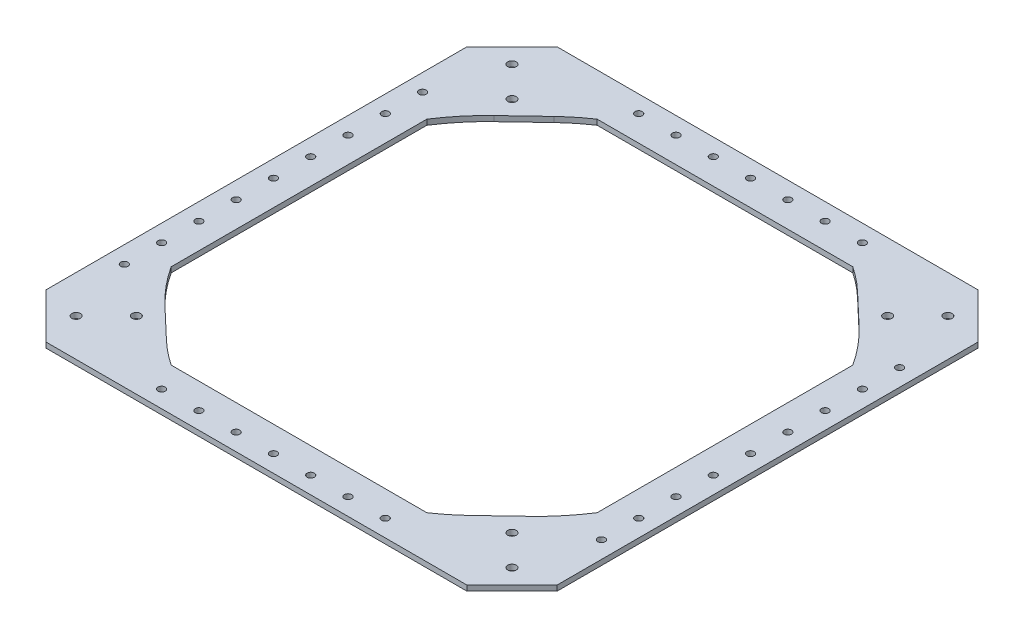
SolidWorks part; units mm, degrees
ref_plane "Front Plane" through (0, 0, 0) normal (0, 0, 1) x (1, 0, 0)
ref_plane "Top Plane" through (0, 0, 0) normal (0, 1, 0) x (1, 0, 0)
ref_plane "Right Plane" through (0, 0, 0) normal (1, 0, 0) x (0, 0, -1)
sketch "Sketch1" plane through (0, 0, 0) normal (0, 1, 0) x (1, 0, 0)
  line L0 (-152.4, 68.2596) -> (-125.4592, 95.2004)
  line L1 (-125.4592, 95.2004) -> (125.4592, 95.2004)
  line L2 (-152.4, 68.2596) -> (-152.4, -182.6588)
  line L3 (152.4, 68.2596) -> (152.4, -182.6588)
  line L4 (152.4, 68.2596) -> (125.4592, 95.2004)
  line L5 (0, 95.2004) -> (0, -209.5996) construction
  line L6 (-152.4, -57.1996) -> (152.4, -57.1996) construction
  line L7 (152.4, -182.6588) -> (125.4592, -209.5996)
  line L8 (-125.4592, -209.5996) -> (125.4592, -209.5996)
  line L9 (-152.4, -182.6588) -> (-125.4592, -209.5996)
  point P9 (0, -57.1996)
  point P11 (0, -57.1996)
  dimension "D1" = 304.8
  dimension "D2" = 304.8
  dimension "D3" = 38.1
  dimension "D4" = 45
extrude "Boss-Extrude1" add sketch "Sketch1" along normal blind 3.175
sketch "Sketch2" plane through (0, 3.175, 0) normal (0, 1, 0) x (1, 0, 0)
  line L0 (-76.2, 69.8004) -> (76.2, 69.8004)
  line L2 (127, -133.3996) -> (127, 19.0004)
  line L3 (90.4661, 58.3749) -> (108.8729, 40.884)
  line L4 (-127, -133.3996) -> (-127, 19.0004)
  line L5 (125.4592, 95.2004) -> (-125.4592, 95.2004) construction
  line L9 (-152.4, 68.2596) -> (-152.4, -182.6588) construction
  line L10 (-125.4592, 95.2004) -> (-152.4, 68.2596) construction
  line L12 (90.4661, -172.7741) -> (108.8729, -155.2832)
  line L13 (-76.2, -184.1996) -> (76.2, -184.1996)
  line L14 (-90.4661, -172.7741) -> (-108.8729, -155.2832)
  line L20 (-125.4592, 95.2004) -> (-90.4661, 58.3749) construction
  line L21 (-125.4592, 95.2004) -> (-143.4197, 77.2399) construction
  line L22 (-143.4197, 77.2399) -> (-108.8729, 40.884) construction
  line L23 (-90.4661, 58.3749) -> (-108.8729, 40.884)
  line L24 (0, 95.2004) -> (0, -259.712) construction
  line L25 (-152.4, -57.1996) -> (213.1094, -57.1996) construction
  arc A0 (-90.4661, 58.3749) -> (-76.2, 69.8004) centre (-15.9731, -20.019) cw
  arc A1 (-108.8729, 40.884) -> (-127, 19.0004) centre (-26.517, -45.7845) ccw
  arc A2 (108.8729, 40.884) -> (127, 19.0004) centre (26.517, -45.7845) cw
  arc A3 (90.4661, 58.3749) -> (76.2, 69.8004) centre (15.9731, -20.019) ccw
  arc A4 (108.8729, -155.2832) -> (127, -133.3996) centre (26.517, -68.6147) ccw
  arc A5 (90.4661, -172.7741) -> (76.2, -184.1996) centre (15.9731, -94.3802) cw
  arc A6 (-90.4661, -172.7741) -> (-76.2, -184.1996) centre (-15.9731, -94.3802) ccw
  arc A7 (-108.8729, -155.2832) -> (-127, -133.3996) centre (-26.517, -68.6147) cw
  point P19 (0, 69.8004)
  point P21 (127, -57.1996)
  point P46 (-127, -57.1996)
  dimension "D1" = 25.4
  dimension "D4" = 25.4
  dimension "D5" = 25.4
  dimension "D9" = 50.8
  dimension "D10" = 76.2
  dimension "D11" = 76.2
extrude "Cut-Extrude1" cut sketch "Sketch2" against normal through all
sketch "Sketch4" plane through (0, 3.175, 0) normal (0, 1, 0) x (1, 0, 0)
  line L0 (-152.4, -57.1996) -> (171.6111, -57.1996) construction
  line L1 (-152.4, 68.2596) -> (-152.4, -182.6588) construction
  line L2 (125.4592, 95.2004) -> (-125.4592, 95.2004) construction
  line L3 (0, -57.1996) -> (0, -217.7016) construction
  line L4 (152.4, -182.6588) -> (152.4, 68.2596) construction
  line L5 (0, -57.1996) -> (0, 293.0757) construction
  circle A0 centre (0, 85.0404) radius 2.159
  circle A1 centre (-44.45, 85.0404) radius 2.159
  circle A2 centre (44.45, 85.0404) radius 2.159
  circle A3 centre (-22.225, 85.0404) radius 2.159
  circle A4 centre (22.225, 85.0404) radius 2.159
  circle A5 centre (-142.24, -57.1996) radius 2.159
  circle A6 centre (-142.24, -34.9746) radius 2.159
  circle A7 centre (-142.24, -12.7496) radius 2.159
  circle A8 centre (142.24, -57.1996) radius 2.159
  circle A9 centre (142.24, -34.9746) radius 2.159
  circle A10 centre (142.24, -12.7496) radius 2.159
  circle A11 centre (142.24, -101.6496) radius 2.159
  circle A12 centre (142.24, -79.4246) radius 2.159
  circle A13 centre (-142.24, -101.6496) radius 2.159
  circle A14 centre (-142.24, -79.4246) radius 2.159
  circle A15 centre (22.225, -199.4396) radius 2.159
  circle A16 centre (-22.225, -199.4396) radius 2.159
  circle A17 centre (44.45, -199.4396) radius 2.159
  circle A18 centre (-44.45, -199.4396) radius 2.159
  circle A19 centre (0, -199.4396) radius 2.159
  circle A20 centre (-66.675, 85.0404) radius 2.159
  circle A21 centre (66.675, 85.0404) radius 2.159
  circle A22 centre (-142.24, 9.4754) radius 2.159
  circle A23 centre (142.24, 9.4754) radius 2.159
  circle A24 centre (142.24, -123.8746) radius 2.159
  circle A25 centre (66.675, -199.4396) radius 2.159
  circle A26 centre (-66.675, -199.4396) radius 2.159
  circle A27 centre (-142.24, -123.8746) radius 2.159
  circle A28 centre (-142.24, -146.0996) radius 2.159
  circle A29 centre (-142.24, 31.7004) radius 2.159
  circle A30 centre (142.24, 31.7004) radius 2.159
  circle A31 centre (142.24, -146.0996) radius 2.159
  point P48 (0, 95.2004)
  dimension "D1" = 4.318
  dimension "D2" = 4.318
  dimension "D3" = 4.318
  dimension "D4" = 4.318
  dimension "D5" = 4.318
  dimension "D6" = 4.318
  dimension "D7" = 4.318
  dimension "D8" = 4.318
  dimension "D9" = 4.318
  dimension "D10" = 4.318
  dimension "D11" = 4.318
  dimension "D23" = 4.318
  dimension "D24" = 4.318
  dimension "D27" = 4.318
  dimension "D28" = 4.318
  dimension "D31" = 4.318
  dimension "D12" = 22.225
  dimension "D13" = 22.225
  dimension "D14" = 22.225
  dimension "D15" = 22.225
  dimension "D16" = 22.225
  dimension "D17" = 22.225
  dimension "D18" = 22.225
  dimension "D19" = 22.225
  dimension "D20" = 10.16
  dimension "D21" = 10.16
  dimension "D22" = 10.16
  dimension "D25" = 22.225
  dimension "D26" = 22.225
  dimension "D29" = 22.225
  dimension "D30" = 22.225
  dimension "D32" = 22.225
extrude "Cut-Extrude2" cut sketch "Sketch4" against normal through all
sketch "Sketch5" plane through (0, 3.175, 0) normal (0, 1, 0) x (1, 0, 0)
  line L0 (0, 95.2004) -> (0, -209.5996) construction
  line L1 (125.4592, 95.2004) -> (-125.4592, 95.2004) construction
  line L2 (152.4, -57.1996) -> (-152.4, -57.1996) construction
  line L3 (152.4, -182.6588) -> (152.4, 68.2596) construction
  line L4 (-125.4592, -209.5996) -> (125.4592, -209.5996) construction
  line L5 (-152.4, 68.2596) -> (-152.4, -182.6588) construction
  line L6 (-255.6729, 198.4733) -> (255.6729, 198.4733) construction
  line L7 (255.6729, 198.4733) -> (255.6729, -312.8725) construction
  line L8 (255.6729, -312.8725) -> (-255.6729, -312.8725) construction
  line L9 (-255.6729, -312.8725) -> (-255.6729, 198.4733) construction
  line L10 (152.4, -57.1996) -> (358.8347, -57.1996) construction
  line L11 (0, 95.2004) -> (0, 301.7463) construction
  line L12 (-255.6729, 198.4733) -> (255.6729, -312.8725) construction
  line L13 (255.6729, 198.4733) -> (-255.6729, -312.8725) construction
  line L14 (-125.4592, 95.2004) -> (-152.4, 68.2596) construction
  circle A0 centre (-129.9494, 72.7498) radius 2.54
  circle A1 centre (-111.9888, 54.7892) radius 2.54
  circle A2 centre (111.9888, 54.7892) radius 2.54
  circle A3 centre (129.9494, 72.7498) radius 2.54
  circle A4 centre (129.9494, -187.149) radius 2.54
  circle A5 centre (111.9888, -169.1884) radius 2.54
  circle A6 centre (-111.9888, -169.1884) radius 2.54
  circle A7 centre (-129.9494, -187.149) radius 2.54
  point P9 (255.6729, -57.1996)
  point P19 (0, 198.4733)
  dimension "D2" = 5.08
  dimension "D3" = 5.08
  dimension "D1" = 165.1
  dimension "D4" = 25.4
  dimension "D5" = 12.7
extrude "Cut-Extrude3" cut sketch "Sketch5" against normal through all
